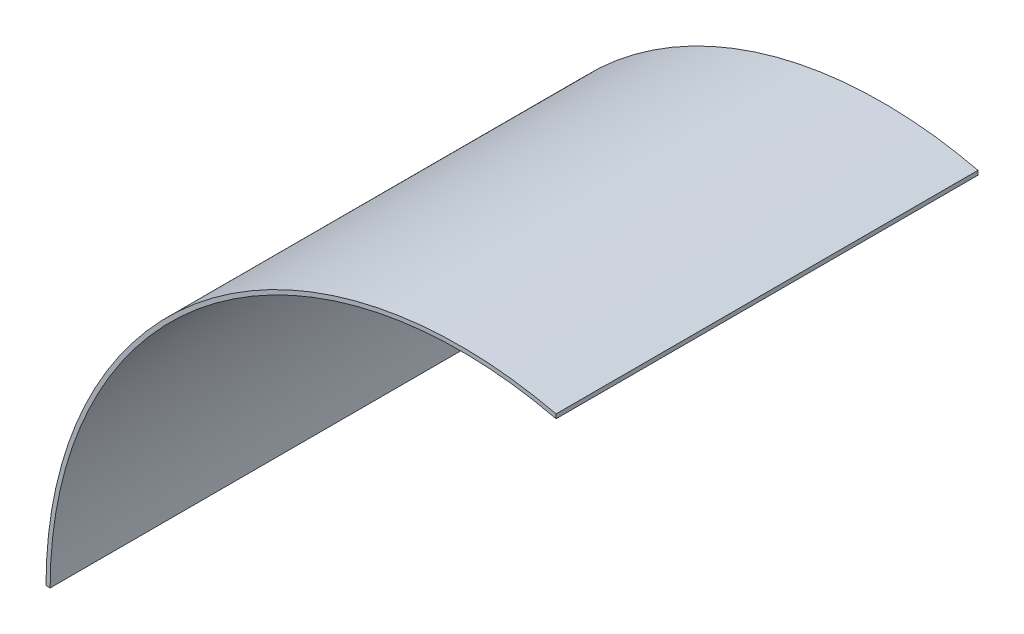
SolidWorks part; units mm, degrees
material "201 Annealed Stainless Steel (SS)"
ref_plane "Front Plane" through (0, 0, 0) normal (0, 0, 1) x (1, 0, 0)
ref_plane "Top Plane" through (0, 0, 0) normal (0, 1, 0) x (1, 0, 0)
ref_plane "Right Plane" through (0, 0, 0) normal (1, 0, 0) x (0, 0, -1)
sketch "Sketch1" plane through (0, 0, 0) normal (0, 0, 1) x (1, 0, 0)
  line L0 (0, 0) -> (0, -152.4) construction
  line L2 (0, 0) -> (101.5936, 0) construction
  line L3 (35, 113.7839) -> (35, -22.985) construction
  line L5 (35, 148.3265) -> (35, 146.7655)
  line L7 (0, 0) -> (-150.8811, 0) construction
  line L10 (32.5, 147.3392) -> (32.5, 148.8943) construction
  line L25 (-152.4, 0) -> (-150.8811, 0)
  circle A0 centre (0, 0) radius 150.8811 construction
  circle A1 centre (0, 0) radius 152.4 construction
  arc A2 (-150.8811, 0) -> (35, 146.7655) centre (0, 0) cw
  arc A3 (-152.4, 0) -> (35, 148.3265) centre (0, 0) cw
  dimension "D1" = 301.7622
  dimension "D2" = 304.8
  dimension "D3" = 35
  dimension "D4" = 5
extrude "Inner Ring - Left Side" add sketch "Sketch1" along normal blind 155
